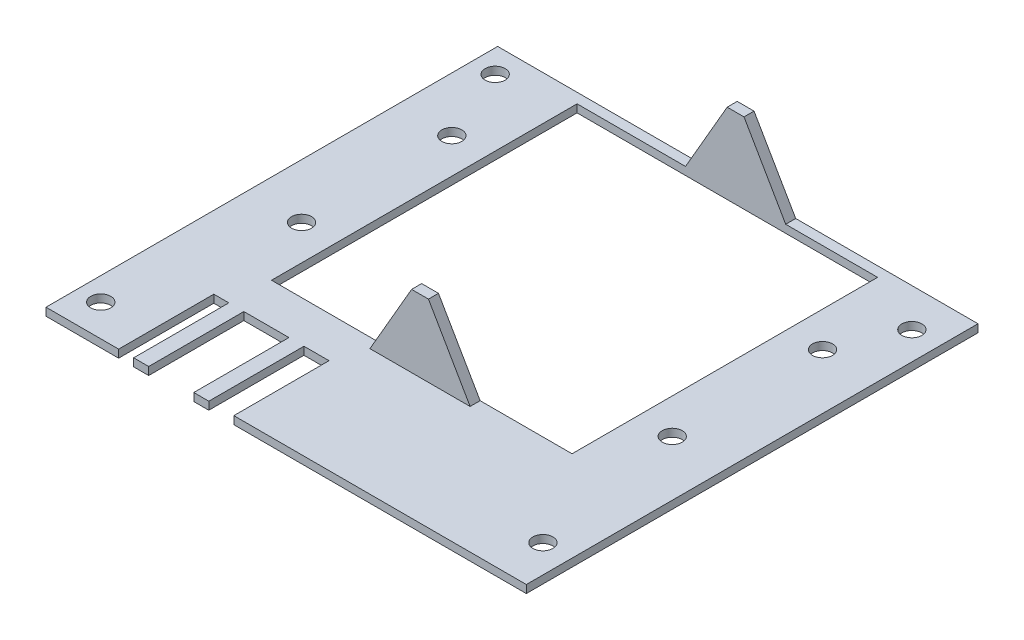
SolidWorks part; units mm, degrees
material "ABS"
ref_plane "Front Plane" through (0, 0, 0) normal (0, 0, 1) x (1, 0, 0)
ref_plane "Top Plane" through (0, 0, 0) normal (0, 1, 0) x (1, 0, 0)
ref_plane "Right Plane" through (0, 0, 0) normal (1, 0, 0) x (0, 0, -1)
sketch "Sketch1" plane through (0, 0, 0) normal (0, 1, 0) x (1, 0, 0)
  line L1 (-32.2441, 108.719) -> (64.6459, 108.719)
  line L2 (-32.2441, 108.719) -> (-32.2441, 18.549)
  line L3 (-32.2441, 18.549) -> (64.6459, 18.549)
  line L4 (64.6459, 108.719) -> (64.6459, 18.549)
  dimension "D1" = 96.89
  dimension "D2" = 90.17
extrude "PCB" add sketch "Sketch1" along normal blind 1.57
sketch "Sketch2" plane through (0, 1.57, 0) normal (0, 1, 0) x (1, 0, 0)
  line L1 (-32.2441, 18.549) -> (64.6459, 18.549) construction
  line L2 (-32.2441, 108.719) -> (-32.2441, 18.549) construction
  line L3 (-32.2441, 18.549) -> (64.6459, 18.549) construction
  circle A0 centre (58.5659, 27.439) radius 2
  circle A1 centre (-27.1641, 24.899) radius 2
  circle A2 centre (-27.1641, 103.639) radius 2
  circle A3 centre (58.5659, 101.099) radius 2
  dimension "D3" = 4
  dimension "D6" = 4
  dimension "D11" = 4
  dimension "D12" = 4
  dimension "D2" = 90.81
  dimension "D4" = 90.81
  dimension "D5" = 6.35
  dimension "D7" = 5.08
  dimension "D8" = 5.08
  dimension "D9" = 82.55
  dimension "D10" = 85.09
  dimension "D13" = 8.89
extrude "M3 Mounting Holes" cut sketch "Sketch2" against normal blind 1.57
sketch "Sketch3" plane through (0, 1.57, 0) normal (0, 1, 0) x (1, 0, 0)
  line L0 (64.6459, 108.719) -> (-32.2441, 108.719) construction
  line L1 (12.7559, 108.719) -> (22.7559, 108.719)
  line L2 (12.7559, 108.719) -> (12.7559, 106.719)
  line L3 (12.7559, 106.719) -> (22.7559, 106.719)
  line L4 (22.7559, 108.719) -> (22.7559, 106.719)
  line L5 (-32.2441, 108.719) -> (-32.2441, 18.549) construction
  line L7 (12.7559, 45.719) -> (22.7559, 45.719)
  line L8 (12.7559, 45.719) -> (12.7559, 43.719)
  line L9 (12.7559, 43.719) -> (22.7559, 43.719)
  line L10 (22.7559, 45.719) -> (22.7559, 43.719)
  dimension "D1" = 2
  dimension "D2" = 10
  dimension "D3" = 0
  dimension "D4" = 45
  dimension "D5" = 61
  dimension "D6" = 2
  dimension "D7" = 45
extrude "Boss-Extrude1" [suppressed] add sketch "Sketch3" along normal blind 10
sketch "Sketch4" plane through (0, 1.57, 0) normal (0, 1, 0) x (1, 0, 0)
  line L0 (64.6459, 108.719) -> (-32.2441, 108.719) construction
  line L1 (64.6459, 108.719) -> (-32.2441, 108.719) construction
  line L2 (-32.2441, 108.719) -> (-32.2441, 18.549) construction
  line L3 (64.6459, 108.719) -> (-32.2441, 108.719) construction
  circle A0 centre (-20.8941, 88.719) radius 2
  circle A1 centre (53.1059, 88.719) radius 2
  circle A2 centre (-20.8941, 58.719) radius 2
  circle A3 centre (53.1059, 58.719) radius 2
  dimension "D1" = 4
  dimension "D2" = 4
  dimension "D7" = 4
  dimension "D8" = 4
  dimension "D12" = 74
  dimension "D3" = 20
  dimension "D4" = 20
  dimension "D5" = 74
  dimension "D6" = 11.35
  dimension "D9" = 50
  dimension "D10" = 50
  dimension "D11" = 11.35
extrude "Cut-Extrude1" cut sketch "Sketch4" against normal blind 23
ref_plane "Plane1" through (0, 0, -45.719) normal (0, 0, 1) x (1, 0, 0)
sketch "Sketch7" plane through (0, 0, -45.719) normal (0, 0, 1) x (1, 0, 0)
  line L0 (27.7559, 1.57) -> (19.4384, 15.9764)
  line L1 (19.4384, 15.9764) -> (16.0735, 15.9764)
  line L2 (16.0735, 15.9764) -> (7.7559, 1.57)
  line L3 (7.7559, 1.57) -> (27.7559, 1.57)
  line L4 (-32.2441, 1.57) -> (64.6459, 1.57) construction
  dimension "D1" = 60
  dimension "D2" = 60
  dimension "D3" = 0
  dimension "D4" = 3.3649
  dimension "D5" = 20
  dimension "D6" = 5
ref_plane "Plane2" through (0, 0, -108.719) normal (0, 0, 1) x (1, 0, 0)
sketch "Sketch8" plane through (0, 0, -108.719) normal (0, 0, 1) x (1, 0, 0)
  line L0 (27.7559, 1.57) -> (19.4384, 15.9764) construction
  line L1 (19.4384, 15.9764) -> (16.0735, 15.9764) construction
  line L2 (16.0735, 15.9764) -> (7.7559, 1.57) construction
  line L3 (7.7559, 1.57) -> (27.7559, 1.57) construction
  line L4 (27.7559, 1.57) -> (19.4384, 15.9764)
  line L5 (19.4384, 15.9764) -> (16.0735, 15.9764)
  line L6 (16.0735, 15.9764) -> (7.7559, 1.57)
  line L7 (7.7559, 1.57) -> (27.7559, 1.57)
extrude "Boss-Extrude2" add sketch "Sketch7" along normal blind 2
extrude "Boss-Extrude3" add sketch "Sketch8" along normal blind 2
sketch "Sketch9" plane through (0, 1.57, 0) normal (0, 1, 0) x (1, 0, 0)
  line L0 (-32.2441, 18.549) -> (64.6459, 18.549) construction
  line L1 (-14.2441, 18.549) -> (-17.2441, 18.549)
  line L2 (-14.2441, 18.549) -> (-14.2441, 37.549)
  line L3 (-14.2441, 37.549) -> (-17.2441, 37.549)
  line L4 (-17.2441, 18.549) -> (-17.2441, 37.549)
  line L5 (-32.2441, 108.719) -> (-32.2441, 18.549) construction
  line L6 (-11.2441, 18.549) -> (-2.2441, 18.549)
  line L7 (-11.2441, 18.549) -> (-11.2441, 37.549)
  line L8 (-11.2441, 37.549) -> (-2.2441, 37.549)
  line L9 (-2.2441, 18.549) -> (-2.2441, 37.549)
  line L11 (0.7559, 18.549) -> (5.7559, 18.549)
  line L12 (0.7559, 18.549) -> (0.7559, 37.549)
  line L13 (0.7559, 37.549) -> (5.7559, 37.549)
  line L14 (5.7559, 18.549) -> (5.7559, 37.549)
  dimension "D1" = 19
  dimension "D2" = 19
  dimension "D3" = 3
  dimension "D4" = 3
  dimension "D5" = 9
  dimension "D6" = 15
  dimension "D7" = 5
  dimension "D8" = 19
  dimension "D9" = 3
extrude "Cut-Extrude2" cut sketch "Sketch9" against normal through all
sketch "Sketch10" plane through (0, 1.57, 0) normal (0, 1, 0) x (1, 0, 0)
  line L0 (7.7559, 108.719) -> (-32.2441, 108.719) construction
  line L1 (-32.2441, 18.549) -> (-31.7441, 18.549)
  line L2 (-32.2441, 18.549) -> (-32.2441, 108.719)
  line L3 (-32.2441, 108.719) -> (-31.7441, 108.719)
  line L4 (-31.7441, 18.549) -> (-31.7441, 108.719)
  line L5 (64.6459, 108.719) -> (27.7559, 108.719) construction
  line L6 (64.6459, 18.549) -> (64.1459, 18.549)
  line L7 (64.6459, 18.549) -> (64.6459, 108.719)
  line L8 (64.6459, 108.719) -> (64.1459, 108.719)
  line L9 (64.1459, 18.549) -> (64.1459, 108.719)
  dimension "D1" = 0.5
  dimension "D2" = 0.5
extrude "Cut-Extrude3" cut sketch "Sketch10" against normal blind 10
sketch "Sketch11" plane through (0, 1.57, 0) normal (0, 1, 0) x (1, 0, 0)
  line L0 (7.7559, 106.719) -> (27.7559, 106.719) construction
  line L1 (-13.8941, 106.719) -> (46.1059, 106.719)
  line L2 (-13.8941, 106.719) -> (-13.8941, 45.719)
  line L3 (-13.8941, 45.719) -> (46.1059, 45.719)
  line L4 (46.1059, 106.719) -> (46.1059, 45.719)
  dimension "D1" = 60
  dimension "D2" = 61
  dimension "D3" = 0
  dimension "D4" = 7
extrude "Cut-Extrude4" cut sketch "Sketch11" against normal blind 10
